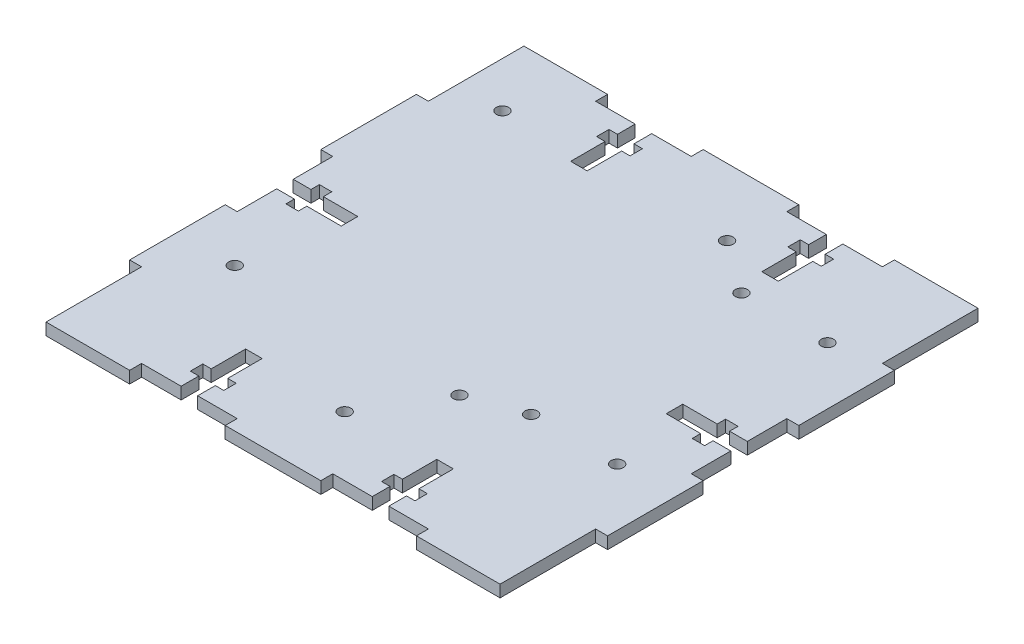
SolidWorks part; units mm, degrees
ref_plane "Front Plane" through (0, 0, 0) normal (0, 0, 1) x (1, 0, 0)
ref_plane "Top Plane" through (0, 0, 0) normal (0, 1, 0) x (1, 0, 0)
ref_plane "Right Plane" through (0, 0, 0) normal (1, 0, 0) x (0, 0, -1)
sketch "Sketch1" plane through (0, 0, 0) normal (0, 1, 0) x (1, 0, 0)
  line L1 (0, 0) -> (127, 0)
  line L2 (0, 0) -> (0, 127)
  line L3 (0, 127) -> (127, 127)
  line L4 (127, 0) -> (127, 127)
  dimension "D1" = 127
  dimension "D2" = 127
extrude "Boss-Extrude1" add sketch "Sketch1" along normal blind 3.175
sketch "Sketch2" plane through (0, 3.175, 0) normal (0, 1, 0) x (1, 0, 0)
  line L1 (0, 127) -> (3.175, 127)
  line L2 (0, 127) -> (0, 101.6)
  line L3 (0, 101.6) -> (3.175, 101.6)
  line L4 (3.175, 127) -> (3.175, 101.6)
  dimension "D1" = 25.4
  dimension "D2" = 3.175
extrude "Cut-Extrude1" cut sketch "Sketch2" against normal blind 6.35
pattern_linear "LPattern1" count 3 spacing 50.8 along (0, 0, 1) count 2 spacing 123.825 along (1, 0, 0) of "Cut-Extrude1"
sketch "Sketch3" plane through (0, 3.175, 0) normal (0, 1, 0) x (1, 0, 0)
  line L0 (3.175, 0) -> (123.825, 0) construction
  line L1 (25.4, 0) -> (50.8, 0)
  line L2 (25.4, 0) -> (25.4, 3.175)
  line L3 (25.4, 3.175) -> (50.8, 3.175)
  line L4 (50.8, 0) -> (50.8, 3.175)
  line L5 (0, 50.8) -> (0, 25.4) construction
  dimension "D1" = 25.4
  dimension "D2" = 3.175
  dimension "D3" = 25.4
extrude "Cut-Extrude2" cut sketch "Sketch3" against normal blind 6.35
pattern_linear "LPattern2" count 3 spacing 50.8 along (1, 0, 0) count 2 spacing 123.825 along (0, 0, -1) of "Cut-Extrude2"
ref_plane "Plane1" through (0, 0, -63.5) normal (0, 0, 1) x (1, 0, 0)
sketch "Sketch4" plane through (0, 3.175, 0) normal (0, 1, 0) x (1, 0, 0)
  line L0 (123.825, 76.2) -> (123.825, 50.8) construction
  line L1 (123.825, 65.6971) -> (106.68, 65.6971)
  line L2 (123.825, 65.6971) -> (123.825, 61.3029)
  line L3 (123.825, 61.3029) -> (106.68, 61.3029)
  line L4 (106.68, 65.6971) -> (106.68, 61.3029)
  line L5 (127, 76.2) -> (123.825, 76.2) construction
  line L7 (115.824, 67.945) -> (119.126, 67.945)
  line L8 (115.824, 67.945) -> (115.824, 59.055)
  line L9 (115.824, 59.055) -> (119.126, 59.055)
  line L10 (119.126, 67.945) -> (119.126, 59.055)
  point P6 (123.825, 63.5)
  point P13 (117.475, 59.055)
  point P14 (119.126, 63.5)
  dimension "D1" = 17.145
  dimension "D2" = 4.3942
  dimension "D3" = 12.7
  dimension "D4" = 3.302
  dimension "D5" = 6.35
  dimension "D6" = 8.89
  dimension "D7" = 12.7
extrude "Cut-Extrude3" cut sketch "Sketch4" against normal blind 8.89 contours L1 L4 L3 L2 | L7 L10 L9 L8
sketch "Sketch5" plane through (0, 3.175, 0) normal (0, 1, 0) x (1, 0, 0)
  line L0 (50.8, 3.175) -> (25.4, 3.175) construction
  line L1 (35.9029, 3.175) -> (40.2971, 3.175)
  line L2 (35.9029, 3.175) -> (35.9029, 20.32)
  line L3 (35.9029, 20.32) -> (40.2971, 20.32)
  line L4 (40.2971, 3.175) -> (40.2971, 20.32)
  line L5 (50.8, 0) -> (50.8, 3.175) construction
  line L6 (33.655, 11.176) -> (42.545, 11.176)
  line L7 (33.655, 11.176) -> (33.655, 7.874)
  line L8 (33.655, 7.874) -> (42.545, 7.874)
  line L9 (42.545, 11.176) -> (42.545, 7.874)
  point P6 (38.1, 20.32)
  point P12 (38.1, 7.874)
  point P15 (42.545, 9.525)
  dimension "D1" = 17.145
  dimension "D2" = 4.3942
  dimension "D3" = 12.7
  dimension "D4" = 3.302
  dimension "D5" = 8.89
  dimension "D6" = 12.7
  dimension "D7" = 6.35
extrude "Cut-Extrude4" cut sketch "Sketch5" against normal blind 30.48 contours L3 L4 L1 L2 | L7 L8 L9 L6
pattern_linear "LPattern3" count 2 spacing 50.8 along (1, 0, 0) of "Cut-Extrude4"
sketch "Sketch10" plane through (0, 3.175, 0) normal (0, 1, 0) x (1, 0, 0)
  line L1 (78.7908, 104.775) -> (101.6, 104.775)
  line L2 (78.7908, 104.775) -> (78.7908, 48.8442)
  line L3 (78.7908, 48.8442) -> (101.6, 48.8442)
  line L4 (101.6, 104.775) -> (101.6, 48.8442)
  line L5 (76.2, 123.825) -> (101.6, 123.825) construction
  line L6 (127, 76.2) -> (127, 101.6) construction
  dimension "D1" = 22.8092
  dimension "D2" = 55.9308
  dimension "D3" = 25.4
  dimension "D4" = 19.05
mirror "Mirror2" about plane through (0, 0, -63.5) normal (0, 0, 1) of "LPattern3"
sketch "2x2_PCB" plane through (0, 3.175, 0) normal (0, 1, 0) x (1, 0, 0)
  line L0 (106.68, 65.6971) -> (106.68, 61.3029) construction
  line L1 (10.16, 90.551) -> (60.96, 90.551)
  line L2 (10.16, 90.551) -> (10.16, 36.449)
  line L3 (10.16, 36.449) -> (60.96, 36.449)
  line L4 (60.96, 90.551) -> (60.96, 36.449)
  line L5 (10.16, 90.551) -> (60.96, 36.449) construction
  line L6 (10.16, 36.449) -> (60.96, 90.551) construction
  line L8 (0, 101.6) -> (0, 76.2) construction
  point P0 (35.56, 63.5)
  point P7 (106.68, 63.5)
  point P8 (35.56, 90.551)
  dimension "D1" = 50.8
  dimension "D2" = 54.102
  dimension "D3" = 35.56
hole_wizard "#4 Clearance Hole4" positions "Sketch18" profile "Sketch16" hole size "#4" standard "ANSI Inch"
sketch "Sketch18" plane through (0, 3.175, 0) normal (0, 1, 0) x (1, 0, 0)
  line L0 (127, 25.4) -> (127, 50.8) construction
  line L2 (50.8, 0) -> (76.2, 0) construction
  point P0 (63.5, 19.05)
  dimension "D1" = 63.5
  dimension "D2" = 19.05
sketch "Sketch16" plane through (63.5, 3.175, -19.05) normal (1, 0, 0) x (0, 0, 1)
  line L0 (0, 0) -> (0, 11.1406)
  line L1 (0, 11.1406) -> (1.6319, 10.16)
  line L2 (1.6319, 10.16) -> (1.6319, 0)
  line L5 (1.6319, 0) -> (0, 0)
  line L10 (0, 11.1406) -> (-1.632, 10.16) construction
  line L11 (0, -6.35) -> (0, 107.95) construction
  dimension "Hole Dia." = 3.2639
  dimension "Hole Depth" = 10.16
  dimension "Drill Angle" = 118
ref_plane "Plane2" through (63.5, 0, 0) normal (-1, 0, 0) x (0, 0, 1)
mirror "Mirror3" about plane through (63.5, 0, 0) normal (-1, 0, 0) of "Cut-Extrude3"
sketch "Sketch19" plane through (0, 3.175, 0) normal (0, 1, 0) x (1, 0, 0)
  line L0 (0, 101.6) -> (0, 76.2) construction
  line L1 (12.7, 111.76) -> (77.47, 111.76)
  line L2 (12.7, 111.76) -> (12.7, 35.56)
  line L3 (12.7, 35.56) -> (77.47, 35.56)
  line L4 (77.47, 111.76) -> (77.47, 35.56)
  line L5 (76.2, 127) -> (50.8, 127) construction
  dimension "D1" = 64.77
  dimension "D2" = 76.2
  dimension "D3" = 12.7
  dimension "D4" = 15.24
hole_wizard "#4 Clearance Hole5" positions "Sketch21" profile "Sketch20" hole size "#4" standard "ANSI Inch"
sketch "Sketch21" plane through (0, 3.175, 0) normal (0, 1, 0) x (1, 0, 0)
  line L0 (12.7, 111.76) -> (12.7, 35.56) construction
  line L1 (12.7, 111.76) -> (77.47, 111.76) construction
  line L2 (77.47, 111.76) -> (77.47, 35.56) construction
  line L3 (12.7, 35.56) -> (77.47, 35.56) construction
  point P0 (15.24, 109.22)
  point P2 (74.93, 109.22)
  point P4 (74.93, 38.1)
  point P6 (15.24, 38.1)
  dimension "D1" = 2.54
  dimension "D2" = 2.54
  dimension "D3" = 2.54
  dimension "D4" = 2.54
sketch "Sketch20" plane through (15.24, 3.175, -109.22) normal (1, 0, 0) x (0, 0, 1)
  line L0 (0, 0) -> (0, 11.1406)
  line L1 (0, 11.1406) -> (1.6319, 10.16)
  line L2 (1.6319, 10.16) -> (1.6319, 0)
  line L5 (1.6319, 0) -> (0, 0)
  line L10 (0, 11.1406) -> (-1.6319, 10.16) construction
  line L11 (0, -6.35) -> (0, 107.95) construction
  dimension "Hole Dia." = 3.2639
  dimension "Hole Depth" = 10.16
  dimension "Drill Angle" = 118
sketch "Sketch22" plane through (0, 3.175, 0) normal (0, 1, 0) x (1, 0, 0)
  line L0 (123.825, 127) -> (101.6, 127) construction
  line L1 (86.36, 101.6) -> (114.3, 101.6)
  line L2 (86.36, 101.6) -> (86.36, 40.64)
  line L3 (86.36, 40.64) -> (114.3, 40.64)
  line L4 (114.3, 101.6) -> (114.3, 40.64)
  line L5 (86.36, 101.6) -> (114.3, 40.64) construction
  line L6 (86.36, 40.64) -> (114.3, 101.6) construction
  line L7 (127, 76.2) -> (127, 101.6) construction
  point P0 (100.33, 71.12)
  dimension "D1" = 27.94
  dimension "D2" = 60.96
  dimension "D3" = 25.4
  dimension "D4" = 12.7
hole_wizard "#4 Clearance Hole6" positions "Sketch24" profile "Sketch23" hole size "#4" standard "ANSI Inch"
sketch "Sketch24" plane through (0, 3.175, 0) normal (0, 1, 0) x (1, 0, 0)
  line L0 (86.36, 101.6) -> (86.36, 40.64) construction
  line L1 (86.36, 101.6) -> (114.3, 101.6) construction
  line L2 (114.3, 101.6) -> (114.3, 40.64) construction
  line L3 (86.36, 40.64) -> (114.3, 40.64) construction
  point P0 (88.9, 99.06)
  point P2 (111.76, 99.06)
  point P4 (111.76, 43.18)
  point P6 (88.9, 43.18)
  dimension "D1" = 2.54
  dimension "D2" = 2.54
  dimension "D3" = 2.54
  dimension "D4" = 2.54
sketch "Sketch23" plane through (88.9, 3.175, -99.06) normal (1, 0, 0) x (0, 0, 1)
  line L0 (0, 0) -> (0, 11.1406)
  line L1 (0, 11.1406) -> (1.6319, 10.16)
  line L2 (1.6319, 10.16) -> (1.6319, 0)
  line L5 (1.6319, 0) -> (0, 0)
  line L10 (0, 11.1406) -> (-1.6319, 10.16) construction
  line L11 (0, -6.35) -> (0, 107.95) construction
  dimension "Hole Dia." = 3.2639
  dimension "Hole Depth" = 10.16
  dimension "Drill Angle" = 118
